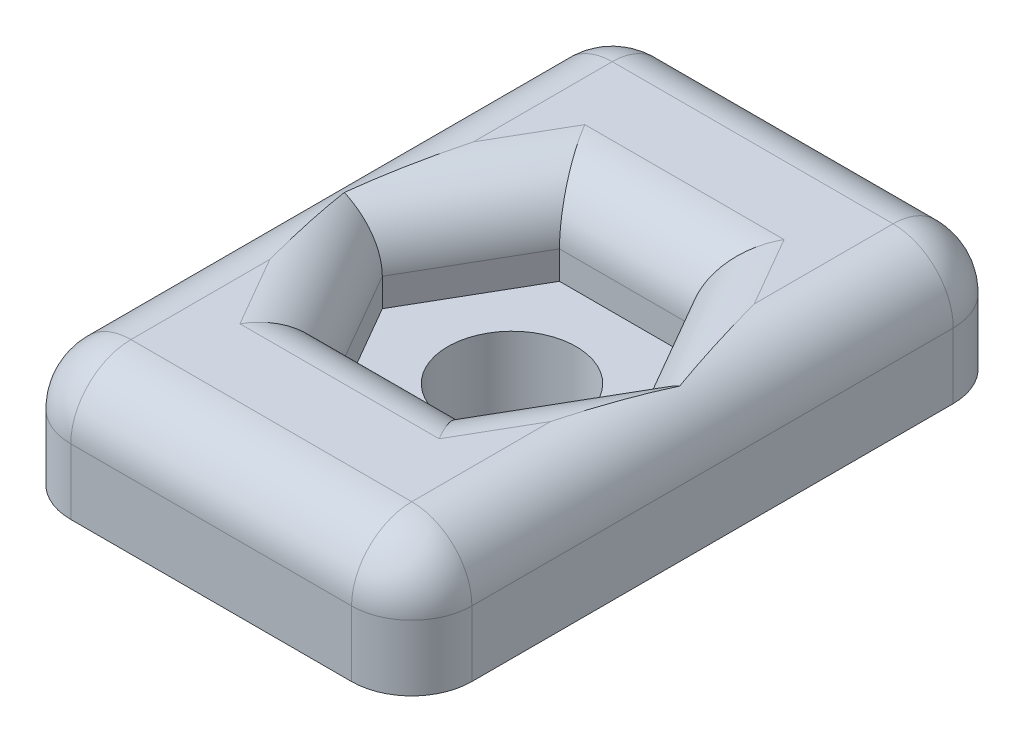
SolidWorks part; units mm, degrees
ref_plane "Front Plane" through (0, 0, 0) normal (0, 0, 1) x (1, 0, 0)
ref_plane "Top Plane" through (0, 0, 0) normal (0, 1, 0) x (1, 0, 0)
ref_plane "Right Plane" through (0, 0, 0) normal (1, 0, 0) x (0, 0, -1)
sketch "Sketch1" plane through (0, 0, 0) normal (0, 1, 0) x (1, 0, 0)
  line L1 (0, 0) -> (10, 0)
  line L2 (0, 0) -> (0, 15)
  line L3 (0, 15) -> (10, 15)
  line L4 (10, 0) -> (10, 15)
  dimension "D1" = 10
  dimension "D2" = 15
extrude "Boss-Extrude1" add sketch "Sketch1" along normal blind 4
sketch "Sketch2" plane through (0, 4, 0) normal (0, 1, 0) x (1, 0, 0)
  line L0 (5, 15) -> (5, 0) construction
  line L1 (10, 15) -> (0, 15) construction
  line L2 (0, 0) -> (10, 0) construction
  line L3 (0, 7.5) -> (10, 7.5) construction
  line L4 (0, 15) -> (0, 0) construction
  line L5 (10, 0) -> (10, 15) construction
  line L7 (8.2332, 7.5) -> (6.6166, 10.3)
  line L8 (6.6166, 10.3) -> (3.3834, 10.3)
  line L9 (3.3834, 10.3) -> (1.7668, 7.5)
  line L10 (1.7668, 7.5) -> (3.3834, 4.7)
  line L11 (3.3834, 4.7) -> (6.6166, 4.7)
  line L12 (6.6166, 4.7) -> (8.2332, 7.5)
  circle A0 centre (5, 7.5) radius 2.8 construction
  dimension "D1" = 5.6
extrude "Cut-Extrude1" cut sketch "Sketch2" against normal blind 2.2
hole_wizard "M3 Clearance Hole1" positions "3DSketch1" profile "Sketch3" hole size "M3" standard "ANSI Metric" end condition through all
sketch3d "3DSketch1"
  line L1 (1.7668, 1.8, -7.5) -> (8.2332, 1.8, -7.5) construction
  line L3 (5, 1.8, -10.3) -> (5, 1.8, -4.7) construction
  line L4 (6.6166, 1.8, -10.3) -> (3.3834, 1.8, -10.3) construction
  line L5 (3.3834, 1.8, -4.7) -> (6.6166, 1.8, -4.7) construction
  point P0 (5, 1.8, -7.5)
  point P22 (5, 1.8, -7.5)
sketch "Sketch3" plane through (5, 1.8, -7.5) normal (1, 0, 0) x (0, 0, 1)
  line L0 (0, 0) -> (0, 1.8)
  line L1 (0, 1.8) -> (1.6, 1.8)
  line L2 (1.6, 1.8) -> (1.6, 0)
  line L5 (1.6, 0) -> (0, 0)
  line L11 (0, -6.35) -> (0, 107.95) construction
  dimension "Thru Hole Dia." = 3.2
  dimension "Thru Hole Depth" = 1.8
fillet "Fillet1" radius 1.5 14 edges at (5, 4, -15) (10, 4, -7.5) (10, 2, -15) (5, 4, 0) (10, 2, 0) (0, 2, -15) (0, 4, -7.5) (0, 2, 0) (5, 4, -10.3) (2.5751, 4, -8.9) (2.5751, 4, -6.1) (5, 4, -4.7) (7.4249, 4, -6.1) (7.4249, 4, -8.9)
chamfer "Chamfer1" distance 1.5 angle 30 8 edges at (10, 0, -7.5) (9.5607, 0, -14.5607) (9.5607, 0, -0.4393) (5, 0, -15) (5, 0, 0) (0.4393, 0, -14.5607) (0.4393, 0, -0.4393) (0, 0, -7.5) first distance on face at (5, 0, -5.9)
